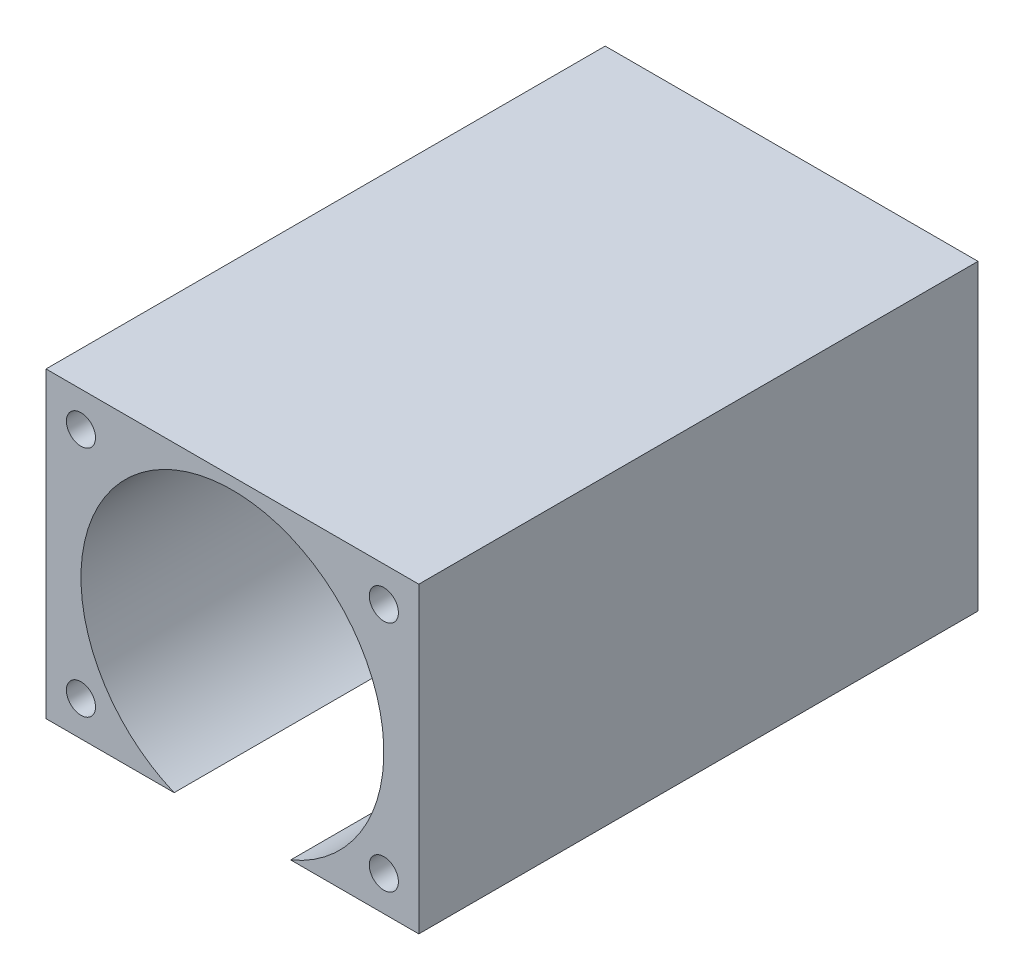
SolidWorks part; units mm, degrees
material "1060 Alloy"
ref_plane "Front Plane" through (0, 0, 0) normal (0, 0, 1) x (1, 0, 0)
ref_plane "Top Plane" through (0, 0, 0) normal (0, 1, 0) x (1, 0, 0)
ref_plane "Right Plane" through (0, 0, 0) normal (1, 0, 0) x (0, 0, -1)
sketch "Sketch1" plane through (0, 0, 0) normal (0, 0, 1) x (1, 0, 0)
  line L0 (-5, -12) -> (-16, -12)
  line L1 (-16, -12) -> (-16, 14)
  line L2 (-16, 14) -> (16, 14)
  line L3 (16, 14) -> (16, -12)
  line L4 (16, -12) -> (5, -12)
  arc A0 (-5, -12) -> (5, -12) centre (0, 0) cw
  dimension "D2" = 13
  dimension "D1" = 32
  dimension "D3" = 26
  dimension "D4" = 14
extrude "Boss-Extrude1" add sketch "Sketch1" along normal blind 48
hole_wizard "Tap Drill for M3 Tap1" positions "3DSketch1" profile "Sketch4" hole size "M3" standard "ISO"
sketch3d "3DSketch1"
  line L0 (-16, 14, 48) -> (-16, -12, 48) construction
  line L1 (16, 14, 48) -> (-16, 14, 48) construction
  line L2 (5, -12, 48) -> (16, -12, 48) construction
  line L3 (16, -12, 48) -> (16, 14, 48) construction
  point P0 (-13, 11, 48)
  point P2 (13, 11, 48)
  point P4 (13, -9, 48)
  point P6 (-13, -9, 48)
  point P8 (-13, -9, 0)
  point P10 (-13, 11, 0)
  point P12 (13, 11, 0)
  point P14 (13, -9, 0)
  dimension "D1" = 3
  dimension "D2" = 3
  dimension "D3" = 3
  dimension "D4" = 3
sketch "Sketch4" plane through (-13, 11, 48) normal (1, 0, 0) x (0, -1, 0)
  line L0 (0, 0) -> (0, 10.7511)
  line L1 (0, 10.7511) -> (1.25, 10)
  line L2 (1.25, 10) -> (1.25, 0)
  line L5 (1.25, 0) -> (0, 0)
  line L10 (0, 10.7511) -> (-1.25, 10) construction
  line L11 (0, -6.35) -> (0, 107.95) construction
  dimension "Hole Dia." = 2.5
  dimension "Hole Depth" = 10
  dimension "Drill Angle" = 118
